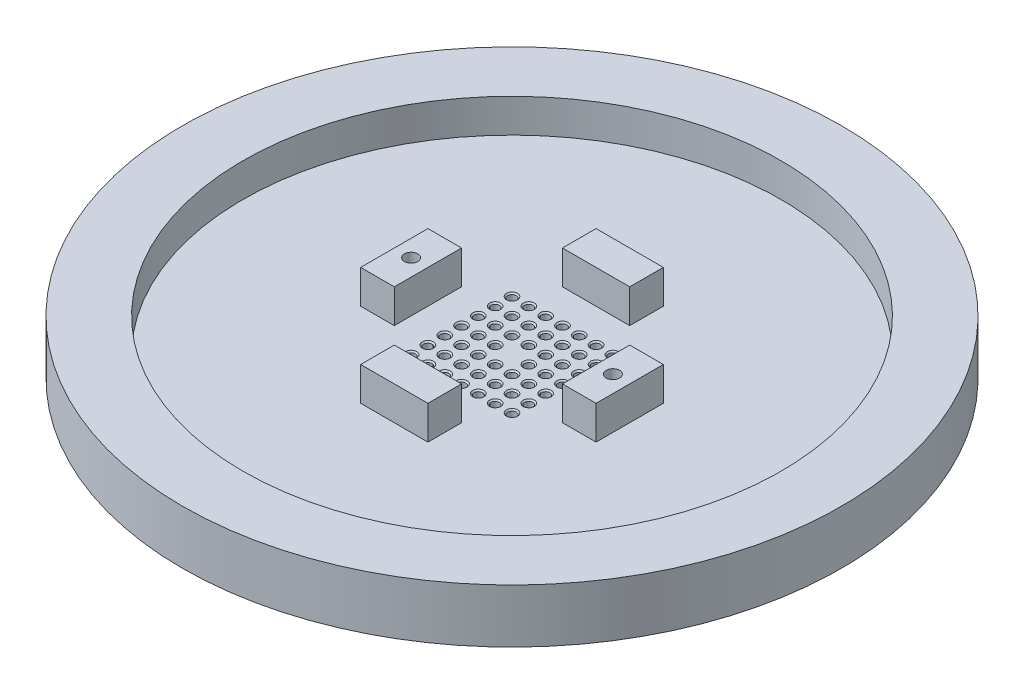
SolidWorks part; units mm, degrees
ref_plane "Front Plane" through (0, 0, 0) normal (0, 0, 1) x (1, 0, 0)
ref_plane "Top Plane" through (0, 0, 0) normal (0, 1, 0) x (1, 0, 0)
ref_plane "Right Plane" through (0, 0, 0) normal (1, 0, 0) x (0, 0, -1)
ref_axis "Axial" through (0, 0.508, 0) along (0, -1, 0)
sketch "Sketch1" plane through (0, 0, 0) normal (0, 1, 0) x (1, 0, 0)
  circle A0 centre (0, 0) radius 62.23
  dimension "D1" = 124.46
extrude "Billet" add sketch "Sketch1" against normal blind 10.16
sketch "Sketch2" plane through (0, 0, 0) normal (0, 1, 0) x (1, 0, 0)
  circle A0 centre (0, 0) radius 50.8
extrude "Manifold Well" cut sketch "Sketch2" against normal blind 6.35
sketch "Sketch4" plane through (0, 0, 0) normal (0, 1, 0) x (1, 0, 0)
  line L0 (0, 37.2675) -> (0, -28.2573) construction
  line L1 (-38.2015, 0) -> (37.6086, 0) construction
  circle A0 centre (9.525, 9.525) radius 0.7937
  dimension "D1" = 1.5875
  dimension "D2" = 9.525
  dimension "D3" = 9.525
extrude "First Kerosene Outlet" cut sketch "Sketch4" against normal through all both
chamfer "Outlet Chamfer" distance 0.254 angle 45 1 edges at (9.525, -6.35, -8.7312)
pattern_linear "Kerosene Outlet Pattern" count 7 spacing 3.175 along (0, 0, 1) count 7 spacing 3.175 along (-1, 0, 0) skipping (3, 3) of "First Kerosene Outlet", "Outlet Chamfer"
sketch "Sketch5" plane through (0, 0, 0) normal (0, 1, 0) x (1, 0, 0)
  line L0 (0, 40.8372) -> (0, -36.9187) construction
  line L1 (-44.3452, 0) -> (47.4284, 0) construction
  line L3 (6.35, 15.875) -> (-6.35, 15.875)
  line L4 (6.35, 15.875) -> (6.35, 22.225)
  line L5 (6.35, 22.225) -> (-6.35, 22.225)
  line L6 (-6.35, 15.875) -> (-6.35, 22.225)
  line L7 (6.35, 15.875) -> (-6.35, 22.225) construction
  line L8 (6.35, 22.225) -> (-6.35, 15.875) construction
  point P5 (0, 19.05)
  dimension "D1" = 6.35
  dimension "D2" = 12.7
  dimension "D3" = 19.05
extrude "LOX Plate Standoff" add sketch "Sketch5" against normal up to next
pattern_circular "Standoff Pattern" count 4 over 360 about axis through (0, 0.508, 0) along (0, -1, 0) of "LOX Plate Standoff"
sketch "Sketch7" plane through (0, -10.16, 0) normal (0, -1, 0) x (1, 0, 0)
  circle A0 centre (0, 0) radius 57.15
  circle A1 centre (0, 0) radius 59.69
  dimension "D1" = 114.3
  dimension "D2" = 119.38
extrude "O-Ring Groove" cut sketch "Sketch7" against normal blind 2.032
sketch "Sketch8" plane through (0, 0, 0) normal (0, 1, 0) x (1, 0, 0)
  circle A0 centre (-19.05, 0) radius 1.27
  point P2 (0, 0)
  dimension "D1" = 2.54
  dimension "D2" = 19.05
extrude "Dowel Hole 1" cut sketch "Sketch8" against normal blind 2.54
pattern_linear "Dowel Hole 2" count 2 spacing 38.1 along (1, 0, 0) of "Dowel Hole 1"
